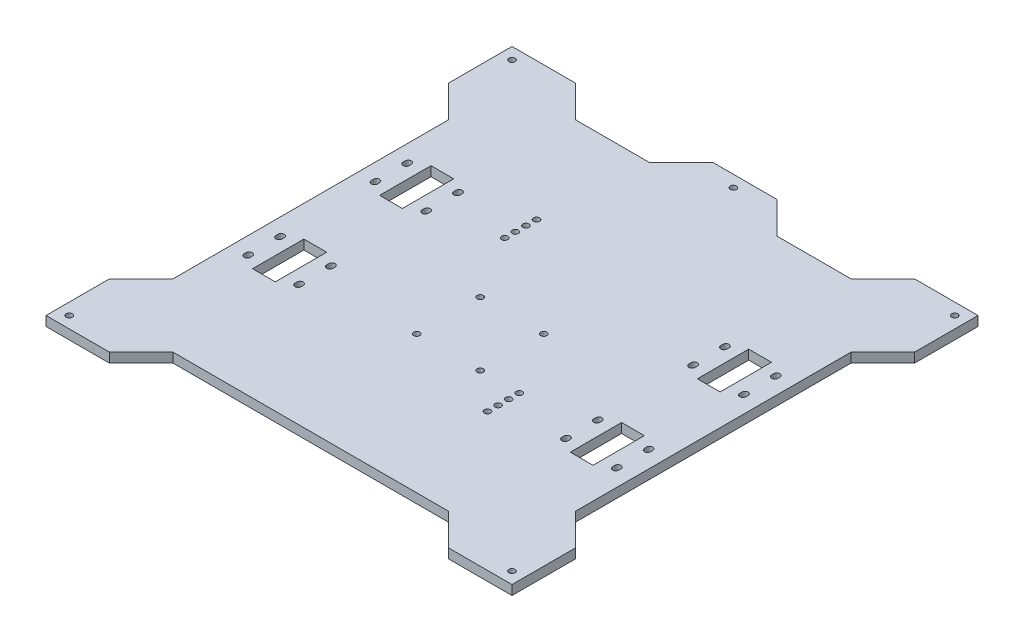
SolidWorks part; units mm, degrees
ref_plane "Front Plane" through (0, 0, 0) normal (0, 0, 1) x (1, 0, 0)
ref_plane "Top Plane" through (0, 0, 0) normal (0, 1, 0) x (1, 0, 0)
ref_plane "Right Plane" through (0, 0, 0) normal (1, 0, 0) x (0, 0, -1)
sketch "Sketch1" plane through (0, 0, 0) normal (0, 1, 0) x (1, 0, 0)
  line L1 (-110, 110) -> (110, 110)
  line L2 (-110, 110) -> (-110, -110)
  line L3 (-110, -110) -> (110, -110)
  line L4 (110, 110) -> (110, -110)
  line L5 (-110, 110) -> (110, -110) construction
  line L6 (-110, -110) -> (110, 110) construction
  point P0 (0, 0)
  dimension "D1" = 220
  dimension "D2" = 220
extrude "Square" add sketch "Sketch1" along normal blind 4.5
sketch "Sketch2" plane through (0, 4.5, 0) normal (0, 1, 0) x (1, 0, 0)
  line L0 (0, 110) -> (0, -110) construction
  line L1 (110, 110) -> (-110, 110) construction
  line L2 (-110, -110) -> (110, -110) construction
  line L3 (-110, 0) -> (110, 0) construction
  line L4 (-110, 110) -> (-110, -110) construction
  line L5 (110, -110) -> (110, 110) construction
  line L6 (75, 110) -> (75, -110) construction
  line L7 (75, 30) -> (0, 30) construction
  line L8 (75, -30) -> (0, -30) construction
  circle A0 centre (87, 38) radius 1.45
  circle A1 centre (87, 22) radius 1.45
  circle A2 centre (63, 22) radius 1.45
  circle A3 centre (63, 38) radius 1.45
  circle A4 centre (-63, 38) radius 1.45
  circle A5 centre (-63, 22) radius 1.45
  circle A6 centre (-87, 22) radius 1.45
  circle A7 centre (-87, 38) radius 1.45
  circle A8 centre (-87, 22) radius 1.45
  circle A9 centre (-87, 38) radius 1.45
  circle A10 centre (-63, 38) radius 1.45
  circle A11 centre (-63, 22) radius 1.45
  circle A12 centre (63, 22) radius 1.45
  circle A13 centre (63, 38) radius 1.45
  circle A14 centre (87, 38) radius 1.45
  circle A15 centre (87, 22) radius 1.45
  circle A16 centre (87, -22) radius 1.45
  circle A17 centre (87, -38) radius 1.45
  circle A18 centre (63, -38) radius 1.45
  circle A19 centre (63, -22) radius 1.45
  circle A20 centre (-63, -22) radius 1.45
  circle A21 centre (-63, -38) radius 1.45
  circle A22 centre (-87, -38) radius 1.45
  circle A23 centre (-87, -22) radius 1.45
  circle A24 centre (-87, -38) radius 1.45
  circle A25 centre (-87, -22) radius 1.45
  circle A26 centre (-63, -22) radius 1.45
  circle A27 centre (-63, -38) radius 1.45
  circle A28 centre (63, -38) radius 1.45
  circle A29 centre (63, -22) radius 1.45
  circle A30 centre (87, -22) radius 1.45
  circle A31 centre (87, -38) radius 1.45
  dimension "D6" = 2.9
  dimension "D7" = 2.9
  dimension "D1" = 75
  dimension "D2" = 30
  dimension "D3" = 16
  dimension "D5" = 12
extrude "LM8UU-Holders" cut sketch "Sketch2" against normal through all contours A7 | A6 | A5 | A4 | A20 | A21 | A22 | A23 | A19 | A18 | A17 | A16 | A1 | A0 | A3 | A2 region at (87, 4.5, -38) region at (87, 4.5, -22) region at (63, 4.5, -22) region at (63, 4.5, -38) region at (-63, 4.5, -38) region at (-63, 4.5, -22) region at (-87, 4.5, -22) region at (-87, 4.5, -38) region at (87, 4.5, 22) region at (87, 4.5, 38) region at (63, 4.5, 38) region at (63, 4.5, 22) region at (-63, 4.5, 22) region at (-63, 4.5, 38) region at (-87, 4.5, 38) region at (-87, 4.5, 22)
sketch "Sketch10" plane through (0, 4.5, 0) normal (0, 1, 0) x (1, 0, 0)
  line L0 (0, 110) -> (0, -79.9796) construction
  line L3 (-26.5242, 0) -> (110, 0) construction
  line L6 (75, 110) -> (75, -110) construction
  line L7 (75, 30) -> (-75, 30) construction
  line L8 (87, 22) -> (87, 23) construction
  line L9 (110, 110) -> (-110, 110) construction
  line L10 (110, -110) -> (110, 110) construction
  line L11 (85.55, 22) -> (85.55, 23)
  line L12 (88.45, 22) -> (88.45, 23)
  line L13 (87, 38) -> (87, 37) construction
  line L14 (88.45, 38) -> (88.45, 37)
  line L15 (85.55, 38) -> (85.55, 37)
  line L16 (63, 38) -> (63, 37) construction
  line L17 (61.55, 38) -> (61.55, 37)
  line L18 (64.45, 38) -> (64.45, 37)
  line L19 (63, 22) -> (63, 23) construction
  line L20 (64.45, 22) -> (64.45, 23)
  line L21 (61.55, 22) -> (61.55, 23)
  line L22 (75, -30) -> (-75, -30) construction
  line L23 (87, -22) -> (87, -23) construction
  line L24 (85.55, -22) -> (85.55, -23)
  line L25 (88.45, -22) -> (88.45, -23)
  line L26 (87, -38) -> (87, -37) construction
  line L27 (88.45, -38) -> (88.45, -37)
  line L28 (85.55, -38) -> (85.55, -37)
  line L29 (63, -38) -> (63, -37) construction
  line L30 (61.55, -38) -> (61.55, -37)
  line L31 (64.45, -38) -> (64.45, -37)
  line L32 (63, -22) -> (63, -23) construction
  line L33 (64.45, -22) -> (64.45, -23)
  line L34 (61.55, -22) -> (61.55, -23)
  line L35 (26.5242, 0) -> (-110, 0) construction
  line L36 (-87, 22) -> (-87, 23) construction
  line L37 (-85.55, 22) -> (-85.55, 23)
  line L38 (-88.45, 22) -> (-88.45, 23)
  line L39 (-87, 38) -> (-87, 37) construction
  line L40 (-88.45, 38) -> (-88.45, 37)
  line L41 (-85.55, 38) -> (-85.55, 37)
  line L42 (-63, 38) -> (-63, 37) construction
  line L43 (-61.55, 38) -> (-61.55, 37)
  line L44 (-64.45, 38) -> (-64.45, 37)
  line L45 (-63, 22) -> (-63, 23) construction
  line L46 (-64.45, 22) -> (-64.45, 23)
  line L47 (-61.55, 22) -> (-61.55, 23)
  line L48 (-87, -22) -> (-87, -23) construction
  line L49 (-85.55, -22) -> (-85.55, -23)
  line L50 (-88.45, -22) -> (-88.45, -23)
  line L51 (-87, -38) -> (-87, -37) construction
  line L52 (-88.45, -38) -> (-88.45, -37)
  line L53 (-85.55, -38) -> (-85.55, -37)
  line L54 (-63, -38) -> (-63, -37) construction
  line L55 (-61.55, -38) -> (-61.55, -37)
  line L56 (-64.45, -38) -> (-64.45, -37)
  line L57 (-63, -22) -> (-63, -23) construction
  line L58 (-64.45, -22) -> (-64.45, -23)
  line L59 (-61.55, -22) -> (-61.55, -23)
  arc A0 (61.55, 38) -> (64.45, 38) centre (63, 38) cw
  arc A1 (88.45, 38) -> (85.55, 38) centre (87, 38) ccw
  arc A2 (85.55, 22) -> (88.45, 22) centre (87, 22) ccw
  arc A3 (88.45, 23) -> (85.55, 23) centre (87, 23) ccw
  arc A4 (85.55, 37) -> (88.45, 37) centre (87, 37) ccw
  arc A5 (64.45, 37) -> (61.55, 37) centre (63, 37) cw
  arc A6 (64.45, 22) -> (61.55, 22) centre (63, 22) cw
  arc A7 (61.55, 23) -> (64.45, 23) centre (63, 23) cw
  arc A8 (85.55, -22) -> (88.45, -22) centre (87, -22) cw
  arc A9 (88.45, -23) -> (85.55, -23) centre (87, -23) cw
  arc A10 (88.45, -38) -> (85.55, -38) centre (87, -38) cw
  arc A11 (85.55, -37) -> (88.45, -37) centre (87, -37) cw
  arc A12 (61.55, -38) -> (64.45, -38) centre (63, -38) ccw
  arc A13 (64.45, -37) -> (61.55, -37) centre (63, -37) ccw
  arc A14 (64.45, -22) -> (61.55, -22) centre (63, -22) ccw
  arc A15 (61.55, -23) -> (64.45, -23) centre (63, -23) ccw
  arc A16 (-85.55, 22) -> (-88.45, 22) centre (-87, 22) cw
  arc A17 (-88.45, 23) -> (-85.55, 23) centre (-87, 23) cw
  arc A18 (-88.45, 38) -> (-85.55, 38) centre (-87, 38) cw
  arc A19 (-85.55, 37) -> (-88.45, 37) centre (-87, 37) cw
  arc A20 (-61.55, 38) -> (-64.45, 38) centre (-63, 38) ccw
  arc A21 (-64.45, 37) -> (-61.55, 37) centre (-63, 37) ccw
  arc A22 (-64.45, 22) -> (-61.55, 22) centre (-63, 22) ccw
  arc A23 (-61.55, 23) -> (-64.45, 23) centre (-63, 23) ccw
  arc A24 (-85.55, -22) -> (-88.45, -22) centre (-87, -22) ccw
  arc A25 (-88.45, -23) -> (-85.55, -23) centre (-87, -23) ccw
  arc A26 (-88.45, -38) -> (-85.55, -38) centre (-87, -38) ccw
  arc A27 (-85.55, -37) -> (-88.45, -37) centre (-87, -37) ccw
  arc A28 (-61.55, -38) -> (-64.45, -38) centre (-63, -38) cw
  arc A29 (-64.45, -37) -> (-61.55, -37) centre (-63, -37) cw
  arc A30 (-64.45, -22) -> (-61.55, -22) centre (-63, -22) cw
  arc A31 (-61.55, -23) -> (-64.45, -23) centre (-63, -23) cw
  point P8 (87, 22.5)
  point P19 (87, 37.5)
  point P28 (63, 37.5)
  point P35 (63, 22.5)
  point P44 (87, -22.5)
  point P51 (87, -37.5)
  point P58 (63, -37.5)
  point P65 (63, -22.5)
  point P73 (0, 30)
  point P74 (0, -30)
  point P76 (-87, 22.5)
  point P83 (-87, 37.5)
  point P90 (-63, 37.5)
  point P97 (-63, 22.5)
  point P104 (-87, -22.5)
  point P111 (-87, -37.5)
  point P118 (-63, -37.5)
  point P125 (-63, -22.5)
  dimension "D1" = 75
  dimension "D2" = 30
  dimension "D3" = 16
  dimension "D5" = 12
  dimension "D4" = 1.45
  dimension "D7" = 1.45
  dimension "D8" = 1
  dimension "D9" = 1
sketch "Sketch3" plane through (0, 4.5, 0) normal (0, 1, 0) x (1, 0, 0)
  line L0 (0, -110) -> (0, 110) construction
  line L1 (-110, -110) -> (110, -110) construction
  line L2 (110, 110) -> (-110, 110) construction
  line L3 (110, -15) -> (-110, -15) construction
  line L6 (15, -30) -> (-15, -30) construction
  line L7 (15, 0) -> (-15, 0) construction
  line L8 (110, -110) -> (110, 110) construction
  line L9 (-110, 110) -> (-110, -110) construction
  line L10 (110, 0) -> (-110, 0) construction
  circle A0 centre (-15, -30) radius 1.45
  circle A1 centre (15, -30) radius 1.45
  circle A2 centre (15, 0) radius 1.45
  circle A3 centre (-15, 0) radius 1.45
  point P16 (0, -30)
  dimension "D1" = 2.9
  dimension "D2" = 15
  dimension "D3" = 15
  dimension "D5" = 15
extrude "DefaultBelt" cut sketch "Sketch3" against normal through all
sketch "Sketch4" plane through (0, 4.5, 0) normal (0, 1, 0) x (1, 0, 0)
  line L0 (0, 110) -> (0, -110) construction
  line L1 (110, 110) -> (-110, 110) construction
  line L2 (-110, -110) -> (110, -110) construction
  line L3 (-15, -1.45) -> (-15, -28.55) construction
  line L4 (15, -28.55) -> (15, -1.45) construction
  line L5 (15, -15) -> (-15, -15) construction
  arc A0 (-0.7348, 6.25) -> (0.7348, 6.25) centre (0, 5) ccw
  arc A1 (0.7348, 6.25) -> (-0.7348, 6.25) centre (0, 7.5) ccw
  arc A2 (0.7348, -36.25) -> (-0.7348, -36.25) centre (0, -37.5) cw
  arc A3 (-0.7348, -36.25) -> (0.7348, -36.25) centre (0, -35) cw
  circle A4 centre (-15, 0) radius 1.45 construction
  circle A5 centre (-15, -30) radius 1.45 construction
  circle A6 centre (15, -30) radius 1.45 construction
  circle A7 centre (15, 0) radius 1.45 construction
  dimension "D1" = 2.9
  dimension "D2" = 2.9
  dimension "D3" = 20
  dimension "D4" = 22.5
extrude "BeltOptions" [suppressed] cut sketch "Sketch4" against normal through all
sketch "Sketch5" plane through (0, 4.5, 0) normal (0, 1, 0) x (1, 0, 0)
  line L0 (-110, 0) -> (110, 0) construction
  line L1 (-110, 110) -> (-110, -110) construction
  line L2 (110, -110) -> (110, 110) construction
  line L3 (0, 110) -> (0, -110) construction
  line L4 (110, 110) -> (-110, 110) construction
  line L5 (-110, 110) -> (-110, 80)
  line L6 (-110, 80) -> (-95, 65)
  line L7 (-95, 65) -> (-95, -65)
  line L8 (0, 0) -> (-110, 110) construction
  line L9 (-65, 95) -> (65, 95)
  line L10 (-80, 110) -> (-65, 95)
  line L11 (-110, 110) -> (-80, 110)
  line L12 (-95, 65) -> (-95, -65)
  line L13 (0, 0) -> (110, 110) construction
  line L14 (95, 65) -> (95, -65)
  line L15 (110, 110) -> (80, 110)
  line L16 (80, 110) -> (65, 95)
  line L17 (95, 65) -> (95, -65)
  line L18 (110, 80) -> (95, 65)
  line L19 (110, 110) -> (110, 80)
  line L20 (0, 0) -> (110, -110) construction
  line L21 (0, 0) -> (-110, -110) construction
  line L22 (110, -110) -> (110, -80)
  line L23 (110, -80) -> (95, -65)
  line L24 (80, -110) -> (65, -95)
  line L25 (110, -110) -> (80, -110)
  line L26 (-110, -110) -> (-80, -110)
  line L27 (-80, -110) -> (-65, -95)
  line L28 (-65, -95) -> (65, -95)
  line L29 (-110, -80) -> (-95, -65)
  line L30 (-110, -110) -> (-110, -80)
  point P24 (0, 95)
  point P32 (95, 0)
  point P35 (-95, 0)
  point P36 (0, -95)
  circle M16 centre (15, -30) radius 1.45
  circle M18 centre (63, 38) radius 1.45
  circle M20 centre (87, 22) radius 1.45
  circle M22 centre (87, -38) radius 1.45
  circle M23 centre (63, -38) radius 1.45
  circle M24 centre (63, -22) radius 1.45
  circle M25 centre (-87, -22) radius 1.45
  circle M26 centre (-87, -38) radius 1.45
  circle M27 centre (-63, -38) radius 1.45
  circle M28 centre (-63, -22) radius 1.45
  circle M29 centre (-63, 38) radius 1.45
  circle M30 centre (-63, 22) radius 1.45
  circle M31 centre (-87, 22) radius 1.45
  circle M32 centre (-87, 38) radius 1.45
  line M33 (110, -110) -> (110, 110)
  line M34 (110, 110) -> (-110, 110)
  line M35 (-110, 110) -> (-110, -110)
  line M36 (-110, -110) -> (110, -110)
  dimension "D1" = 15
  dimension "D2" = 30
  dimension "D3" = 45
  dimension "D4" = 45
extrude "Shaping" cut sketch "Sketch5" against normal blind 10 flip side to cut contours L29 L27 L28 L24 L23 L14 L18 L16 L9 L10 L6 L7 M35 M36 M33 M34 M16 M18 M20 M22 M24 M26 M28 M30 M32 M31 M29 M27 M25 M23 region at (0.037, 4.5, -0.0113)
sketch "Sketch6" plane through (0, 4.5, 0) normal (0, 1, 0) x (1, 0, 0)
  line L0 (-110, 110) -> (110, -110) construction
  line L1 (-110, -110) -> (110, 110) construction
  line L2 (110, 80) -> (110, 110) construction
  line L3 (0, 95) -> (0, -95) construction
  line L4 (-65, 95) -> (65, 95) construction
  line L5 (-65, -95) -> (65, -95) construction
  line L6 (-95, 0) -> (95, 0) construction
  line L7 (-95, 65) -> (-95, -65) construction
  line L8 (95, 65) -> (95, -65) construction
  circle A0 centre (-104.5, 104.5) radius 1.45
  circle A1 centre (104.5, 104.5) radius 1.45
  circle A2 centre (104.5, -104.5) radius 1.45
  circle A3 centre (-104.5, -104.5) radius 1.45
  dimension "D2" = 2.9
  dimension "D1" = 45
  dimension "D3" = 104.5
extrude "Cut-Extrude5" cut sketch "Sketch6" against normal through all
sketch "Sketch7" plane through (0, 4.5, 0) normal (0, 1, 0) x (1, 0, 0)
  line L0 (-87, 38) -> (-63, 22) construction
  line L1 (-63, 22) -> (-87, 22) construction
  line L2 (-87, 22) -> (-63, 38) construction
  line L3 (-63, 38) -> (-87, 38) construction
  line L4 (-95, 0) -> (95, 0) construction
  line L5 (-80.375, 42.125) -> (-69.625, 42.125)
  line L6 (-80.375, 42.125) -> (-80.375, 17.875)
  line L7 (-80.375, 17.875) -> (-69.625, 17.875)
  line L8 (-69.625, 42.125) -> (-69.625, 17.875)
  line L9 (-80.375, 42.125) -> (-69.625, 17.875) construction
  line L10 (-80.375, 17.875) -> (-69.625, 42.125) construction
  line L11 (-95, 65) -> (-95, -65) construction
  line L12 (95, 65) -> (95, -65) construction
  line L13 (0, -95) -> (0, 95) construction
  line L14 (-65, -95) -> (65, -95) construction
  line L15 (-65, 95) -> (65, 95) construction
  line L16 (-80.375, -17.875) -> (-69.625, -42.125) construction
  line L17 (-80.375, -42.125) -> (-69.625, -17.875) construction
  line L18 (-63, -38) -> (-87, -38) construction
  line L19 (-87, -22) -> (-63, -38) construction
  line L20 (-63, -22) -> (-87, -22) construction
  line L21 (-87, -38) -> (-63, -22) construction
  line L22 (-69.625, -42.125) -> (-69.625, -17.875)
  line L23 (-80.375, -17.875) -> (-69.625, -17.875)
  line L24 (-80.375, -42.125) -> (-80.375, -17.875)
  line L25 (-80.375, -42.125) -> (-69.625, -42.125)
  line L26 (-80.375, 17.875) -> (-69.625, 42.125) construction
  line L27 (80.375, 17.875) -> (69.625, 42.125) construction
  line L28 (87, -38) -> (63, -22) construction
  line L29 (63, -22) -> (87, -22) construction
  line L30 (87, -22) -> (63, -38) construction
  line L31 (63, -38) -> (87, -38) construction
  line L32 (80.375, -42.125) -> (69.625, -17.875) construction
  line L33 (80.375, -17.875) -> (69.625, -42.125) construction
  line L34 (80.375, 17.875) -> (69.625, 42.125) construction
  line L35 (80.375, 42.125) -> (69.625, 17.875) construction
  line L36 (63, 38) -> (87, 38) construction
  line L37 (87, 22) -> (63, 38) construction
  line L38 (63, 22) -> (87, 22) construction
  line L39 (87, 38) -> (63, 22) construction
  line L40 (80.375, -42.125) -> (69.625, -42.125)
  line L41 (80.375, -42.125) -> (80.375, -17.875)
  line L42 (80.375, -17.875) -> (69.625, -17.875)
  line L43 (69.625, -42.125) -> (69.625, -17.875)
  line L44 (69.625, 42.125) -> (69.625, 17.875)
  line L45 (80.375, 17.875) -> (69.625, 17.875)
  line L46 (80.375, 42.125) -> (80.375, 17.875)
  line L47 (80.375, 42.125) -> (69.625, 42.125)
  point P4 (-75, 30)
  point P33 (-75, -30)
  point P50 (75, -30)
  point P51 (75, 30)
  dimension "D1" = 10.75
  dimension "D2" = 24.25
extrude "Cut-Extrude6" cut sketch "Sketch7" against normal through all
sketch "Sketch8" plane through (0, 4.5, 0) normal (0, 1, 0) x (1, 0, 0)
  line L0 (0, 0) -> (0, 95) construction
  line L1 (0, 0) -> (-66.8115, 0) construction
  line L3 (-65, 95) -> (65, 95) construction
  line L4 (-33.45, 45) -> (-33.45, 30) construction
  line L5 (-33.45, 45) -> (-33.45, 30) construction
  line L6 (33.45, -45) -> (33.45, -30) construction
  circle A0 centre (-33.45, 45) radius 1.45
  circle A1 centre (-33.45, 40) radius 1.45
  circle A2 centre (-33.45, 35) radius 1.45
  circle A3 centre (-33.45, 30) radius 1.45
  circle A8 centre (33.45, -45) radius 1.45
  circle A9 centre (33.45, -40) radius 1.45
  circle A10 centre (33.45, -35) radius 1.45
  circle A11 centre (33.45, -30) radius 1.45
  dimension "D1" = 2.9
  dimension "D2" = 50
  dimension "D4" = 33.45
extrude "EndstopTrigger" cut sketch "Sketch8" against normal through all
pattern_linear "LPattern1" [suppressed] count 2 spacing 30 of bodies 108
sketch "Sketch9" plane through (0, 4.5, 0) normal (0, 1, 0) x (1, 0, 0)
  line L0 (-80, 110) -> (-110, 110) construction
  line L1 (-65, 95) -> (65, 95) construction
  line L7 (-95, 0) -> (95, 0) construction
  line L8 (-95, 65) -> (-95, -65) construction
  line L11 (95, 65) -> (95, -65) construction
  line L12 (-104.5, 104.5) -> (104.5, 104.5) construction
  line L13 (0, 110) -> (0, 95) construction
  line L14 (-80, 110) -> (80, 110) construction
  line L15 (15, 110) -> (30, 95)
  line L16 (-30, 95) -> (30, 95)
  line L17 (-15, 110) -> (-30, 95)
  line L18 (15, 110) -> (-15, 110)
  circle A1 centre (0, 104.5) radius 1.45
  dimension "D2" = 30
  dimension "D3" = 2.9
  dimension "D1" = 45
  dimension "D4" = 45
extrude "Boss-Extrude1" add sketch "Sketch9" against normal through all
extrude "HolesToSlots" cut sketch "Sketch10" against normal through all
sketch "Sketch11" plane through (0, 4.5, 0) normal (0, 1, 0) x (1, 0, 0)
  line L0 (0, -95) -> (0, 0) construction
  line L1 (-65, -95) -> (65, -95) construction
  line L2 (95, 0) -> (0, 0) construction
  line L3 (95, 65) -> (95, -65) construction
  line L4 (0, 0) -> (110, -110) construction
  line L5 (-69.1421, -85) -> (-5, -85)
  line L6 (-69.1421, -85) -> (-84.1421, -100)
  line L7 (-84.1421, -100) -> (-100, -100)
  line L8 (-100, -100) -> (-100, -84.1421)
  line L9 (-100, -84.1421) -> (-85, -69.1421)
  line L10 (-85, -69.1421) -> (-85, -52.125)
  line L11 (-85, -52.125) -> (-5, -52.125)
  line L12 (-80, -110) -> (-65, -95) construction
  line L13 (-110, -80) -> (-95, -65) construction
  line L14 (-110, -80) -> (-110, -110) construction
  line L15 (-110, -110) -> (-80, -110) construction
  line L16 (-80.375, -42.125) -> (-69.625, -42.125) construction
  line L17 (-95, 65) -> (-95, -65) construction
  line L18 (-5, -52.125) -> (-5, -85)
  line L19 (5, -52.125) -> (5, -85)
  line L20 (85, -52.125) -> (5, -52.125)
  line L21 (85, -69.1421) -> (85, -52.125)
  line L22 (100, -84.1421) -> (85, -69.1421)
  line L23 (100, -100) -> (100, -84.1421)
  line L24 (84.1421, -100) -> (100, -100)
  line L25 (69.1421, -85) -> (84.1421, -100)
  line L26 (69.1421, -85) -> (5, -85)
  line L27 (69.1421, 85) -> (5, 85)
  line L28 (69.1421, 85) -> (84.1421, 100)
  line L29 (84.1421, 100) -> (100, 100)
  line L30 (100, 100) -> (100, 84.1421)
  line L31 (100, 84.1421) -> (85, 69.1421)
  line L32 (85, 69.1421) -> (85, 52.125)
  line L33 (85, 52.125) -> (5, 52.125)
  line L34 (5, 52.125) -> (5, 85)
  line L35 (-5, 52.125) -> (-5, 85)
  line L36 (-85, 52.125) -> (-5, 52.125)
  line L37 (-85, 69.1421) -> (-85, 52.125)
  line L38 (-100, 84.1421) -> (-85, 69.1421)
  line L39 (-100, 100) -> (-100, 84.1421)
  line L40 (-84.1421, 100) -> (-100, 100)
  line L41 (-69.1421, 85) -> (-84.1421, 100)
  line L42 (-69.1421, 85) -> (-5, 85)
  dimension "D1" = 10
  dimension "D2" = 10
  dimension "D3" = 10
  dimension "D4" = 10
  dimension "D5" = 10
  dimension "D6" = 10
  dimension "D7" = 10
  dimension "D8" = 5
extrude "Cut-Extrude7" [suppressed] cut sketch "Sketch11" against normal through all
sketch "Sketch12" [suppressed] plane through (0, 4.5, 0) normal (0, 1, 0) x (1, 0, 0)
  line L0 (0, 0) -> (-110, -110) construction
  line L1 (-110, -110) -> (-80, -110) construction
  line L2 (-110, -80) -> (80, 110) construction
  line L3 (110, 80) -> (-80, -110) construction
  line L4 (-95, -65) -> (-65, -95) construction
  line L5 (0, 0) -> (0, -95) construction
  line L6 (-65, -95) -> (65, -95) construction
  line L7 (95, 0) -> (-95, 0) construction
  line L8 (-95, 65) -> (-95, -65) construction
  line L9 (-100, -100) -> (-100, -84.1421)
  line L10 (-100, -84.1421) -> (-59.2893, -43.4315)
  line L11 (-59.2893, -43.4315) -> (-43.4315, -43.4315)
  line L12 (-110, -80) -> (-110, -110) construction
  line L13 (-100, -100) -> (-84.1421, -100)
  line L14 (-84.1421, -100) -> (-43.4315, -59.2893)
  line L15 (-43.4315, -59.2893) -> (-43.4315, -43.4315)
  line L16 (55, -85) -> (-55, -85)
  line L17 (-55, -85) -> (-29.2893, -59.2893)
  line L18 (-29.2893, -59.2893) -> (29.2893, -59.2893)
  line L19 (95, -65) -> (65, -95) construction
  line L20 (0, 0) -> (110, -110) construction
  line L21 (55, -85) -> (29.2893, -59.2893)
  line L22 (43.4315, -59.2893) -> (43.4315, -43.4315)
  line L23 (84.1421, -100) -> (43.4315, -59.2893)
  line L24 (100, -100) -> (84.1421, -100)
  line L25 (59.2893, -43.4315) -> (43.4315, -43.4315)
  line L26 (100, -84.1421) -> (59.2893, -43.4315)
  line L27 (100, -100) -> (100, -84.1421)
  line L28 (95, 65) -> (65, 95) construction
  line L29 (-95, 65) -> (-65, 95) construction
  line L30 (100, 100) -> (100, 84.1421)
  line L31 (100, 84.1421) -> (59.2893, 43.4315)
  line L32 (59.2893, 43.4315) -> (43.4315, 43.4315)
  line L33 (100, 100) -> (84.1421, 100)
  line L34 (84.1421, 100) -> (43.4315, 59.2893)
  line L35 (43.4315, 59.2893) -> (43.4315, 43.4315)
  line L36 (55, 85) -> (29.2893, 59.2893)
  line L37 (-29.2893, 59.2893) -> (29.2893, 59.2893)
  line L38 (-55, 85) -> (-29.2893, 59.2893)
  line L39 (55, 85) -> (-55, 85)
  line L40 (-43.4315, 59.2893) -> (-43.4315, 43.4315)
  line L41 (-84.1421, 100) -> (-43.4315, 59.2893)
  line L42 (-100, 100) -> (-84.1421, 100)
  line L43 (-59.2893, 43.4315) -> (-43.4315, 43.4315)
  line L44 (-100, 84.1421) -> (-59.2893, 43.4315)
  line L45 (-100, 100) -> (-100, 84.1421)
  point P40 (0, -59.2893)
  point P41 (0, -85)
  point P67 (0, 85)
  point P68 (0, 59.2893)
  dimension "D1" = 10
  dimension "D2" = 10
  dimension "D3" = 80
  dimension "D4" = 10
  dimension "D5" = 10
  dimension "D6" = 0
extrude "Cut-Extrude8" [suppressed] cut sketch "Sketch12" against normal through all
sketch "Sketch14" [suppressed] plane through (0, 4.5, 0) normal (0, 1, 0) x (1, 0, 0)
  line L0 (0, 85) -> (0, 110) construction
  line L1 (55, 85) -> (-55, 85) construction
  line L2 (15, 110) -> (-15, 110) construction
  line L3 (10.8579, 100) -> (-10.8579, 100)
  line L4 (-10.8579, 100) -> (-25.8579, 85)
  line L5 (-25.8579, 85) -> (25.8579, 85)
  line L6 (-15, 110) -> (-30, 95) construction
  line L7 (10.8579, 100) -> (25.8579, 85)
  point P13 (0, 100)
  dimension "D1" = 10
  dimension "D2" = 10
extrude "Cut-Extrude10" [suppressed] cut sketch "Sketch14" against normal through all
sketch "Sketch13" [suppressed] plane through (0, 4.5, 0) normal (0, 1, 0) x (1, 0, 0)
  line L0 (-59.2893, 43.4315) -> (-59.2893, -43.4315) construction
  line L1 (-100, 84.1421) -> (-59.2893, 43.4315) construction
  line L2 (-59.2893, 0) -> (0, 0) construction
  line L3 (-59.2893, 33.4315) -> (-59.2893, -33.4315)
  line L4 (-59.2893, -33.4315) -> (-43.4315, -33.4315)
  line L5 (-43.4315, -33.4315) -> (-43.4315, 33.4315)
  line L6 (-43.4315, 33.4315) -> (-59.2893, 33.4315)
  line L7 (-59.2893, 43.4315) -> (-43.4315, 43.4315) construction
  line L8 (-43.4315, -43.4315) -> (-59.2893, -43.4315) construction
  line L9 (-43.4315, 43.4315) -> (-43.4315, 59.2893) construction
  line L10 (0, 0) -> (0, 43.4315) construction
  line L11 (59.2893, 43.4315) -> (59.2893, -43.4315) construction
  line L12 (43.4315, 33.4315) -> (59.2893, 33.4315)
  line L13 (43.4315, -33.4315) -> (43.4315, 33.4315)
  line L14 (59.2893, -33.4315) -> (43.4315, -33.4315)
  line L15 (59.2893, 33.4315) -> (59.2893, -33.4315)
  line L16 (110, -110) -> (0, 0) construction
  line L17 (55, -85) -> (29.2893, -59.2893) construction
  line L18 (-33.4315, -43.2893) -> (33.4315, -43.2893)
  line L19 (-33.4315, -43.2893) -> (-33.4315, -63.4315)
  line L20 (-33.4315, -63.4315) -> (33.4315, -63.4315)
  line L21 (33.4315, -43.2893) -> (33.4315, -63.4315)
  line L22 (-33.4315, -43.2893) -> (33.4315, -63.4315) construction
  line L23 (-33.4315, -63.4315) -> (33.4315, -43.2893) construction
  line L24 (-43.4315, -59.2893) -> (-43.4315, -43.4315) construction
  line L25 (0, -53.3604) -> (0, -63.4315) construction
  line L26 (55, 85) -> (25.8579, 85) construction
  line L28 (43.4315, -43.4315) -> (43.4315, -59.2893) construction
  line L29 (29.2893, -59.2893) -> (-29.2893, -59.2893) construction
  line L30 (43.4315, 59.2893) -> (43.4315, 43.4315) construction
  line L31 (-33.4315, 83) -> (33.4315, 83)
  line L32 (-33.4315, 83) -> (-33.4315, 15)
  line L33 (-33.4315, 15) -> (33.4315, 15)
  line L34 (33.4315, 83) -> (33.4315, 15)
  line L35 (-33.4315, 83) -> (33.4315, 15) construction
  line L36 (-33.4315, 15) -> (33.4315, 83) construction
  point P27 (0, -53.3604)
  point P43 (0, 49)
  dimension "D1" = 10
  dimension "D2" = 10
  dimension "D3" = 10
  dimension "D4" = 10
  dimension "D5" = 16
  dimension "D6" = 10
  dimension "D7" = 10
  dimension "D8" = 15
  dimension "D9" = 2
extrude "Cut-Extrude9" [suppressed] cut sketch "Sketch13" against normal through all
sketch "Sketch15" [suppressed] plane through (0, 4.5, 0) normal (0, 1, 0) x (1, 0, 0)
  line L0 (-59.2893, 0) -> (-95, 0) construction
  line L1 (-59.2893, 33.4315) -> (-59.2893, -33.4315) construction
  line L2 (-95, 65) -> (-95, -65) construction
  line L3 (-80.5, 17.875) -> (-69.5, 17.875) construction
  line L4 (-59.2893, -15) -> (-59.2893, -7.875)
  line L5 (-85, -7.875) -> (-85, 7.875)
  line L6 (-85, 7.875) -> (-66.4143, 7.875)
  line L7 (-59.2893, -7.875) -> (-59.2893, 7.875)
  line L8 (-66.4143, -7.875) -> (-59.2893, -15)
  line L9 (-85, -7.875) -> (-66.4143, -7.875)
  line L11 (-66.4143, 7.875) -> (-59.2893, 15)
  line L12 (-59.2893, 15) -> (-59.2893, 7.875)
  line L13 (0, 0) -> (0, -21.7485) construction
  line L14 (59.2893, 0) -> (95, 0) construction
  line L15 (59.2893, 15) -> (59.2893, 7.875)
  line L16 (66.4143, 7.875) -> (59.2893, 15)
  line L17 (85, -7.875) -> (66.4143, -7.875)
  line L18 (66.4143, -7.875) -> (59.2893, -15)
  line L19 (59.2893, -7.875) -> (59.2893, 7.875)
  line L20 (85, 7.875) -> (66.4143, 7.875)
  line L21 (85, -7.875) -> (85, 7.875)
  line L22 (59.2893, -15) -> (59.2893, -7.875)
  line L23 (-59.2893, 0) -> (-95, 0) construction
  point P17 (-85, 0)
  point P30 (85, 0)
  dimension "D1" = 10
  dimension "D2" = 10
  dimension "D4" = 45
  dimension "D5" = 15
extrude "Cut-Extrude11" [suppressed] cut sketch "Sketch15" against normal through all
sketch "Sketch16" [suppressed] plane through (0, 4.5, 0) normal (0, 1, 0) x (1, 0, 0)
  line L0 (-85, -69.1421) -> (-85, -52.125)
  line L1 (-59.2893, -43.4315) -> (-100, -84.1421) construction
  line L2 (-85, -52.125) -> (-67.9829, -52.125)
  line L3 (-67.9829, -52.125) -> (-85, -69.1421)
  line L4 (-95, 65) -> (-95, -65) construction
  line L5 (-80.5, -42.125) -> (-69.5, -42.125) construction
  line L6 (-95, 0) -> (95, 0) construction
  line L7 (95, 65) -> (95, -65) construction
  line L8 (0, 0) -> (0, -95) construction
  line L9 (-65, -95) -> (65, -95) construction
  line L10 (-67.9829, 52.125) -> (-85, 69.1421)
  line L11 (-85, 52.125) -> (-67.9829, 52.125)
  line L12 (-85, 69.1421) -> (-85, 52.125)
  line L13 (-67.9829, -52.125) -> (-85, -69.1421)
  line L14 (67.9829, -52.125) -> (85, -69.1421)
  line L15 (85, 69.1421) -> (85, 52.125)
  line L16 (85, 52.125) -> (67.9829, 52.125)
  line L17 (67.9829, 52.125) -> (85, 69.1421)
  line L18 (67.9829, -52.125) -> (85, -69.1421)
  line L19 (85, -52.125) -> (67.9829, -52.125)
  line L20 (85, -69.1421) -> (85, -52.125)
  line L21 (100, -84.1421) -> (59.2893, -43.4315) construction
  line L23 (69.5, -42.125) -> (80.5, -42.125) construction
  line L24 (80.5, 42.125) -> (69.5, 42.125) construction
  line L25 (59.2893, 43.4315) -> (100, 84.1421) construction
  line L26 (-100, 84.1421) -> (-59.2893, 43.4315) construction
  line L27 (-69.5, 42.125) -> (-80.5, 42.125) construction
  dimension "D1" = 10
  dimension "D2" = 10
  dimension "D3" = 10
  dimension "D4" = 10
  dimension "D5" = 10
  dimension "D6" = 10
  dimension "D7" = 10
  dimension "D8" = 10
extrude "Cut-Extrude12" [suppressed] cut sketch "Sketch16" against normal through all contours L3 L2 L0 | L10 L12 L11 | L17 L16 L15 | L14 L20 L19
equation "\"X-ROD-SPACING\"=45"
equation "\"Y-ROD-SPACING\"=75"
equation "\"Z-ROD-SPACING\"=17.5"
equation "\"Y-BED-OFFSET\"=2"
equation "\"Y-BED-ROD-INSET\"=3.5"
equation "\"T-SLOT-NUT-FILLET-RADIUS\"=0.5"
equation "\"T-SLOT-SCREW-SHAFT-RADIUS\"=1.55"
equation "\"T-SLOT-SCREW-SHAFT-CUTOUT-LENGTH\"=11.0"
equation "\"T-SLOT-NUT-DEPTH\"=3.5"
equation "\"T-SLOT-NUT-WIDTH\"=2.85"
equation "\"T-SLOT-NUT-END-DISTANCE\"=8"
equation "\"ACRYLIC-THICKNESS\"=10"
equation "\"ACRYLIC-THICKNESS2\"=4.5"
equation "\"ACRYLIC-TAB-CUTOUT-SIZE\"=\"ACRYLIC-THICKNESS\"+\"ACRYLIC-TAB-TOLERANCE\"*2"
equation "\"ACRYLIC-TAB-WIDTH\"=\"ACRYLIC-THICKNESS\""
equation "\"ACRYLIC-M3-HOLE\"=2.9"
equation "\"SMOOTHROD-CAP-SCREW-DISTANCE\"=20"
equation "\"FRAME-WIDTH-INNER\"=370"
equation "\"NEMA17-HOLE-SPACING\"=31"
equation "\"NEMA17-CENTRAL-CUTOUT\"=22.5"
equation "\"Z-BRACKET-REACH\"=55"
equation "\"TOP-BRACKET-SPACING\"=40"
equation "\"SMOOTHROD-X-LENGTH\"=350"
equation "\"SMOOTHROD-Y-LENGTH\"=350"
equation "\"SMOOTHROD-Z-LENGTH\"=350"
equation "\"SMOOTHROD-TIGHTENING-HEADROOM\"=.25"
equation "\"LEADSCREW-Z-LENGTH\"=300"
equation "\"SCREW-LENGTH-FRAME\"=\"ACRYLIC-THICKNESS\" + 10"
equation "\"SCREW-HEAD-RADIUS\"=6"
equation "\"PRINTED-X-SMOOTHROD-DIAMETER\"=9.0"
equation "\"PRINTED-X-SMOOTHROD-CUTOUT\"=10"
equation "\"PRINTED-X-BASE-HEIGHT\"=10"
equation "\"PRINTED-LM8UU-CUTOUT-SIZE\"=15.5"
equation "\"PRINTED-LM8UU-CUTOUT-LENGTH\"=24.5"
equation "\"PRINTED-X-IDLER-HEIGHT\"=16"
equation "\"PSU-MOUNTING-WIDTH\"=95"
equation "\"PSU-MOUNTING-HEIGHT\"=177"
equation "\"Y-BELT-TO-ROD-DISTANCE\"=20"
equation "\"D6@Sketch2\"=\"ACRYLIC-M3-HOLE\""
equation "\"D7@Sketch2\"=\"ACRYLIC-M3-HOLE\""
equation "\"D1@Sketch2\"=\"Y-ROD-SPACING\""
equation "\"D1@Sketch3\"=\"ACRYLIC-M3-HOLE\""
equation "\"D2@Sketch6\"=\"ACRYLIC-M3-HOLE\""
equation "\"Y-BED-SCREW-SPACING\"=209"
equation "\"Y-BED-SCREW-CUTOUT-SLOT-HEIGHT\"=2"
equation "\"ACRYLIC-TAB-TOLERANCE\"=-.05"
equation "\"Z-ROD-INSET\"=16"
equation "\"SCREW-LENGTH-MOTOR\"=\"ACRYLIC-THICKNESS\" + 5"
equation "\"SCREW-LENGTH-EXTRUDER\"=28"
equation "\"PRINTED-M3-HOLE\"=3.5"
equation "\"SPOOL-HOLDER-ROD-SPACING\"=150"
equation "\"ACRYLIC-X-CARRIAGE-WIDTH\"=55"
equation "\"ACRYLIC-X-CARRIAGE-HEIGHT\"=75"
equation "\"ACRYLIC-X-CARRIAGE-LM8UU-CUTOUT-WIDTH\"=24.25"
equation "\"ACRYLIC-X-CARRIAGE-LM8UU-CUTOUT-HEIGHT\"=11.0"
equation "\"ACRYLIC-X-CARRIAGE-SCREW-SPACING-X\"=15"
equation "\"ACRYLIC-X-CARRIAGE-SCREW-SPACING-Y\"=33"
equation "\"ACRYLIC-X-CARRIAGE-CENTER-TAB-SPACING\"=14"
equation "\"ACRYLIC-X-CARRIAGE-EXTRUDER-OFFSET\"=26"
equation "\"ACRYLIC-X-CARRIAGE-EXTRUDER-ANGLE\"=90"
equation "\"ACRYLIC-X-CARRIAGE-EXTRUDER-SHELF-DEPTH\"=\"ACRYLIC-X-CARRIAGE-EXTRUDER-OFFSET\" + 28"
equation "\"ACRYLIC-X-CARRIAGE-EXTRUDER-BRACE-SPACING\"=23"
equation "\"ACRYLIC-X-CARRIAGE-EXTRUDER-BRACE-TAB-OFFSET\"=20"
equation "\"ACRYLIC-X-CARRIAGE-EXTRUDER-BRACE-HEIGHT\"=35"
equation "\"ACRYLIC-X-CARRIAGE-EXTRUDER-BRACE-SCREW-SPACING\"=22"
equation "\"ACRYLIC-X-CARRIAGE-DUAL-WIDTH-MULTIPLIER\"=1.65"
equation "\"ACRYLIC-X-CARRIAGE-DUAL-HOTEND-SPACING\"=42"
equation "\"ACRYLIC-X-CARRIAGE-DUAL-WIDTH\"=75"
equation "\"ACRYLIC-X-CARRIAGE-DUAL-HOTEND-SEPARATION\"=36"
equation "\"ACRYLIC-X-CARRIAGE-DUAL-MOUNT-PLATE-DEPTH\"=75"
equation "\"ACRYLIC-X-CARRIAGE-DUAL-MOUNT-BRACE-WIDTH\"=33"
equation "\"ACRYLIC-X-CARRIAGE-DUAL-MOUNT-SCREW-WIDTH\"=40"
equation "\"BLOWER-FAN-WIDTH\"=15"
equation "\"D2@Sketch7\"=\"ACRYLIC-X-CARRIAGE-LM8UU-CUTOUT-WIDTH\""
equation "\"D1@Sketch8\"=\"ACRYLIC-M3-HOLE\""
equation "\"D2@Sketch4\"=\"ACRYLIC-M3-HOLE\""
equation "\"D1@Sketch4\"=\"ACRYLIC-M3-HOLE\""
equation "\"D3@Sketch4\"=20"
equation "\"D3@Sketch9\"=\"ACRYLIC-M3-HOLE\""
equation "\"D4@Sketch10\"=\"ACRYLIC-M3-HOLE\"/2"
equation "\"D7@Sketch10\"=\"ACRYLIC-M3-HOLE\" / 2"
